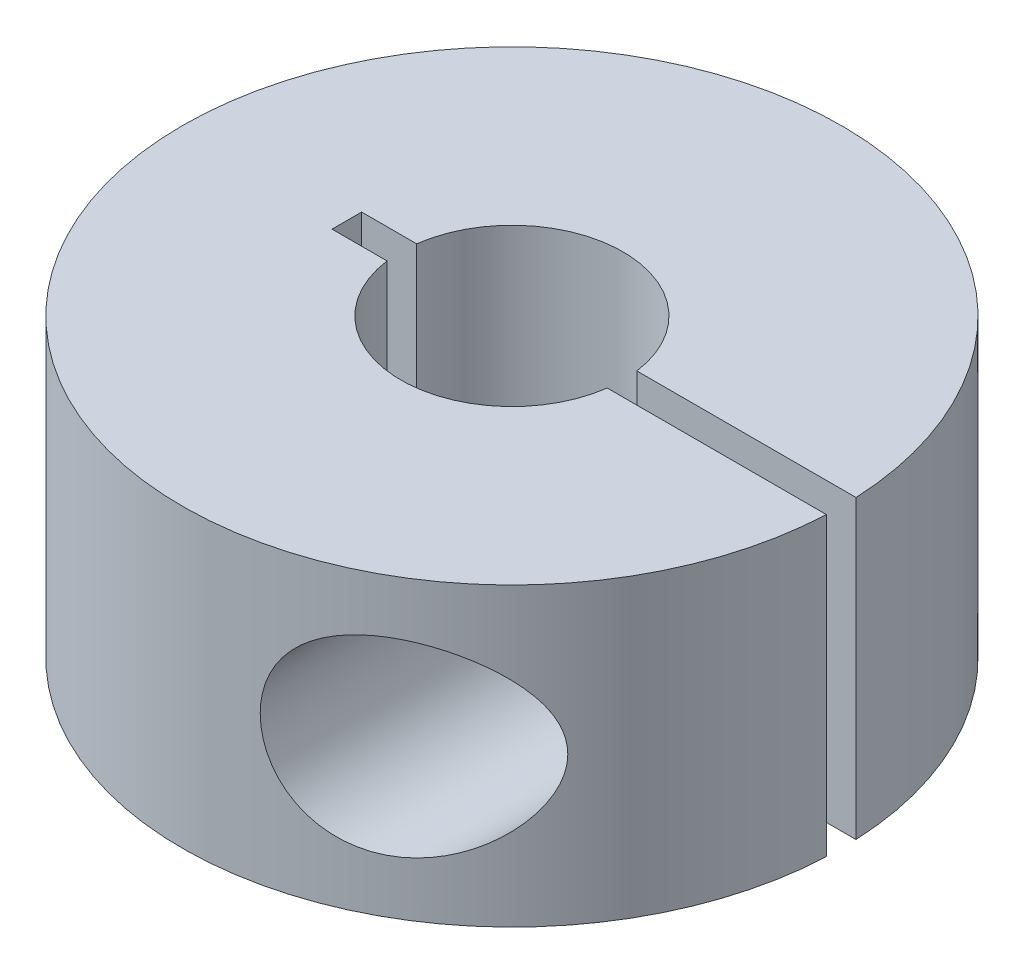
SolidWorks part; units mm, degrees
ref_plane "Front Plane" through (0, 0, 0) normal (0, 0, 1) x (1, 0, 0)
ref_plane "Top Plane" through (0, 0, 0) normal (0, 1, 0) x (1, 0, 0)
ref_plane "Right Plane" through (0, 0, 0) normal (1, 0, 0) x (0, 0, -1)
sketch "Sketch1" plane through (0, 0, 0) normal (0, 1, 0) x (1, 0, 0)
  circle A0 centre (0, 0) radius 11.125
  dimension "D1" = 22.25
extrude "Boss-Extrude1" add sketch "Sketch1" along normal blind 10
ref_plane "Plane1" through (0, 0, -3) normal (0, 0, 1) x (1, 0, 0)
sketch "Sketch2" plane through (0, 0, -3) normal (0, 0, 1) x (1, 0, 0)
  line L0 (0, 5) -> (11.125, 5) construction
  line L1 (11.125, 10) -> (-11.125, 10) construction
  line L2 (0, 0) -> (0, 10) construction
  line L3 (11.125, 0) -> (11.125, 10) construction
  line L5 (4.3581, 2.8954) -> (6.783, 2.9047)
  line L6 (6.783, 2.9047) -> (7.9874, 5.0093)
  line L7 (7.9874, 5.0093) -> (6.7669, 7.1046)
  line L8 (6.7669, 7.1046) -> (4.342, 7.0953)
  line L9 (4.342, 7.0953) -> (3.1376, 4.9907)
  line L10 (3.1376, 4.9907) -> (4.3581, 2.8954)
  circle A0 centre (5.5625, 5) radius 2.1 construction
  point P1 (0, 10)
  point P9 (5.5625, 5)
  dimension "D1" = 4.2
  dimension "D2" = 2.4249
extrude "Cut-Extrude1" cut sketch "Sketch2" against normal through all
sketch "Sketch3" plane through (0, 0, 0) normal (0, 1, 0) x (1, 0, 0)
  line L0 (-5.5735, 0.5) -> (-5.5735, -0.5)
  line L5 (-5.5735, -0.5) -> (11.4265, -0.5)
  line L6 (11.4265, -0.5) -> (11.4265, 0.5)
  line L12 (11.4265, 0.5) -> (-5.5735, 0.5)
  line L13 (-5.5735, 0) -> (11.4265, 0) construction
  point P3 (-0.5735, 0.5)
  point P7 (0, 0)
  dimension "D1" = 5
  dimension "D2" = 12
  dimension "D3" = 1
extrude "Cut-Extrude2" cut sketch "Sketch3" along normal through all
ref_plane "Plane2" through (0, 0, 4.6) normal (0, 0, 1) x (1, 0, 0)
sketch "Sketch6" plane through (0, 0, 4.6) normal (0, 0, 1) x (1, 0, 0)
  line L0 (0, 5) -> (11.125, 5) construction
  point P0 (5.5625, 5)
hole_wizard "CBORE for M2 Hex Head Machine Screw1" positions "Sketch6" profile "Sketch7" counterbore size "M2" standard "ANSI Metric" end condition through all
sketch "Sketch7" plane through (5.5625, 5, 4.6) normal (1, 0, 0) x (0, -1, 0)
  line L0 (0, 0) -> (0, 15.725)
  line L1 (0, 15.725) -> (1.2, 15.725)
  line L3 (1.2, 15.725) -> (1.2, 1.6)
  line L4 (1.2, 1.6) -> (3.19, 1.6)
  line L5 (3.19, 1.6) -> (3.19, 0)
  line L7 (3.19, 0) -> (0, 0)
  line L11 (0, -6.35) -> (0, 107.95) construction
  dimension "Thru Hole Dia." = 2.4
  dimension "Thru Hole Depth" = 15.725
  dimension "C'Bore Dia." = 6.38
  dimension "C'Bore Depth" = 1.6
sketch "Sketch8" plane through (0, 0, 4.6) normal (0, 0, 1) x (1, 0, 0)
  circle A0 centre (5.5625, 5) radius 3.19
  dimension "D1" = 6.38
extrude "Cut-Extrude3" cut sketch "Sketch8" along normal through all
sketch "Sketch9" plane through (0, 0, 0) normal (0, 1, 0) x (1, 0, 0)
  circle A0 centre (0, 0) radius 3.75
  dimension "AxleHoleDiameter" = 7.5
extrude "Cut-Extrude4" cut sketch "Sketch9" along normal through all both and the other way through all
sketch "Sketch10" plane through (0, 0, 0) normal (0, 0, 1) x (1, 0, 0)
  line L0 (0, 0) -> (0, 10) construction
  line L2 (3.7165, 10) -> (-3.7165, 10) construction
ref_axis "Axis1" through (0, 0, 0) along (0, 1, 0)
